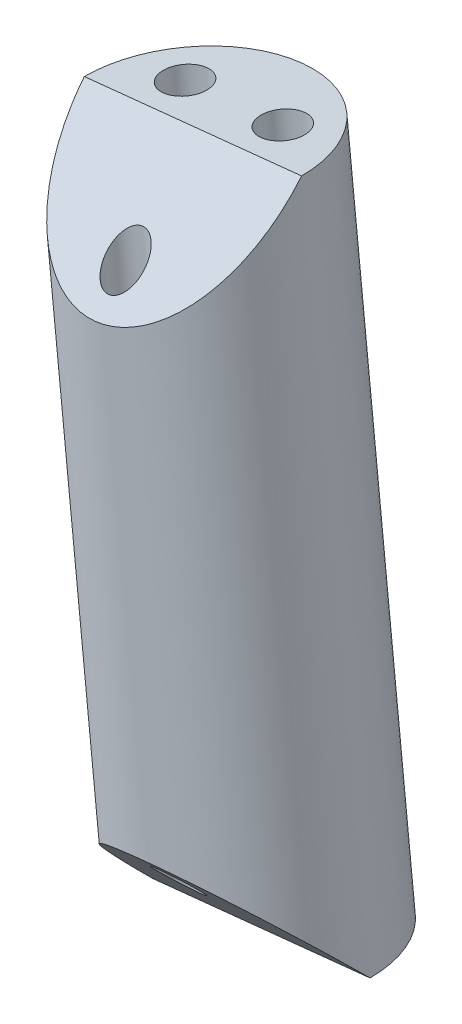
SolidWorks part; units mm, degrees
ref_plane "Front Plane" through (0, 0, 0) normal (0, 0, 1) x (1, 0, 0)
ref_plane "Top Plane" through (0, 0, 0) normal (0, 1, 0) x (1, 0, 0)
ref_plane "Right Plane" through (0, 0, 0) normal (1, 0, 0) x (0, 0, -1)
sketch "Sketch2" plane through (0, 0, 0) normal (0, 0, 1) x (1, 0, 0)
  line L0 (0, 0) -> (90, 0)
  line L1 (90, 0) -> (90, 120)
  line L2 (90, 120) -> (0, 120)
  line L3 (0, 120) -> (0, 0)
  line L4 (0, 120) -> (-10, 120)
  line L5 (-10, 120) -> (-10, 16.9491)
  line L6 (-10, 120) -> (57.5, 127)
  line L7 (57.5, 127) -> (90, 124)
  line L8 (90, 120) -> (99, 60)
  line L10 (90, 124) -> (90, 120)
  line L11 (5.9147, 0) -> (5.9147, -25)
  line L12 (5.9147, -25) -> (-4.0853, -25)
  line L13 (-4.0853, -29) -> (-4.0853, 0)
  line L14 (80, 0) -> (80, -25)
  line L15 (80, -25) -> (90, -25)
  line L16 (90, -29) -> (90, 0)
  line L17 (15.7927, 122.6748) -> (5.4776, 222.1414)
  line L18 (5.4776, 222.1414) -> (21.3923, 223.7918)
  line L19 (21.3923, 223.7918) -> (31.7073, 124.3252)
  line L20 (7.6492, 201.201) -> (23.5639, 202.8514)
  line L21 (10.9066, 169.7905) -> (26.8212, 171.441)
  line L22 (-10, 120) -> (-20.0396, 216.8108)
  line L23 (-20.0396, 216.8108) -> (-4.125, 218.4612)
  line L24 (-4.125, 218.4612) -> (5.9147, 121.6504)
  line L25 (-17.926, 196.4296) -> (-2.0114, 198.08)
  line L26 (-14.7556, 165.8578) -> (1.159, 167.5082)
  line L27 (57.5, 127) -> (46.9095, 229.1223)
  line L28 (46.9095, 229.1223) -> (30.9949, 227.4719)
  line L29 (30.9949, 227.4719) -> (41.5853, 125.3496)
  line L30 (33.2245, 205.9725) -> (49.1391, 207.6229)
  line L31 (36.5688, 173.7233) -> (52.4835, 175.3737)
  line L34 (90, 124) -> (99.1917, 223.5767)
  line L35 (99.1917, 223.5767) -> (83.2594, 225.0473)
  line L36 (83.2594, 225.0473) -> (74.0677, 125.4707)
  line L38 (81.3243, 204.0838) -> (97.2566, 202.6132)
  line L39 (78.4217, 172.6386) -> (94.354, 171.1679)
  line L40 (62.4078, 79.6749) -> (57.5, 127) construction
  line L41 (41.5853, 125.3496) -> (46.4931, 78.0244) construction
  line L42 (46.4931, 78.0244) -> (62.4078, 79.6749) construction
  line L43 (31.7073, 124.3252) -> (36.6151, 77.0001) construction
  line L44 (36.6151, 77.0001) -> (20.7005, 75.3496) construction
  line L45 (20.7005, 75.3496) -> (15.7927, 122.6748) construction
  line L46 (5.9147, 121.6504) -> (10.8224, 74.3253) construction
  line L47 (10.8224, 74.3253) -> (-5.0922, 72.6749) construction
  line L48 (-5.0922, 72.6749) -> (-10, 120) construction
  line L49 (74.0677, 125.4707) -> (69.6944, 78.0931) construction
  line L50 (69.6944, 78.0931) -> (85.7624, 78.0931) construction
  line L51 (85.7624, 78.0931) -> (90, 124) construction
  line L52 (-12.0823, 217.636) -> (10.4873, 0) construction
  line L53 (13.4349, 222.9666) -> (36.5574, 0) construction
  line L54 (38.9522, 228.2971) -> (62.6275, 0) construction
  line L55 (91.2256, 224.312) -> (70.5198, 0) construction
  line L59 (99, 60) -> (93.5277, 44.9649)
  line L60 (99, 60) -> (169.4769, 34.3485)
  line L61 (169.4769, 34.3485) -> (164.0046, 19.3134)
  line L62 (164.0046, 19.3134) -> (93.5277, 44.9649)
  line L63 (90, -2) -> (100, -2)
  line L64 (141.2862, 44.6091) -> (135.8138, 29.574)
  line L65 (99, 60) -> (55.7741, 75.7329) construction
  line L66 (55.7741, 75.7329) -> (50.3018, 60.6978) construction
  line L67 (100, -2) -> (100, -29)
  line L70 (-4.0853, -2) -> (-14.0853, -2)
  line L71 (-14.0853, -2) -> (-14.0853, -29)
  line L74 (-4.0853, 0) -> (0, 0)
  line L75 (-14.0853, -29) -> (-14.0853, -112.587)
  line L76 (-14.0853, -112.587) -> (100, -112.587)
  line L77 (100, -112.587) -> (100, -29)
  line L78 (-14.0853, -29) -> (100, -29)
  line L79 (-14.0853, -14.5) -> (100, -14.5) construction
  line L80 (31.7073, -112.587) -> (31.7073, -122.6232)
  line L81 (31.7073, -122.6232) -> (42.9573, -122.6232)
  line L82 (42.9573, -122.6232) -> (42.9573, -112.587)
  line L83 (-14.0853, -112.587) -> (-88.3667, -112.587)
  line L84 (-88.3667, -112.587) -> (-88.3667, -128.2699)
  line L85 (-88.3667, -128.2699) -> (169.4958, -128.2699)
  line L86 (169.4958, -128.2699) -> (169.4958, -112.587)
  line L87 (169.4958, -112.587) -> (100, -112.587)
  line L88 (90, 60) -> (-10, 60) construction
  line L89 (50.3018, 60.6978) -> (93.5277, 44.9649) construction
  line L90 (87.2806, 55.7521) -> (166.7408, 26.8309) construction
  line L91 (87.2806, 55.7521) -> (82.1749, 52.5336) construction
  line L92 (82.1749, 52.5336) -> (77.3257, 0) construction
  line L93 (83.1185, 56.6957) -> (86.337, 51.59) construction
  arc A0 (-10, 16.9491) -> (-4.0853, 0) centre (14.9876, 16.1624) ccw
  arc A1 (93.5277, 44.9649) -> (90, 0) centre (-126.4069, 39.5988) cw
  point P42 (41.1818, 206.7977)
  point P100 (84.7278, 54.1428)
  point P101 (84.7278, 54.1428)
  dimension "D11" = 47.3684
  dimension "D35" = 9
  dimension "D32" = 220
  dimension "D36" = 25
  dimension "D1" = 120
  dimension "D2" = 90
  dimension "D3" = 10
  dimension "D5" = 67.862
  dimension "D6" = 7
  dimension "D7" = 4
  dimension "D8" = 16
  dimension "D9" = 16
  dimension "D10" = 100
  dimension "D12" = 31.5789
  dimension "D13" = 16
  dimension "D14" = 16
  dimension "D15" = 16
  dimension "D16" = 25.7927
  dimension "D17" = 100
  dimension "D18" = 21.0526
  dimension "D19" = 31.5789
  dimension "D20" = 97.33
  dimension "D21" = 102.67
  dimension "D22" = 20.4905
  dimension "D23" = 30.7358
  dimension "D24" = 21.6147
  dimension "D25" = 32.4221
  dimension "D26" = 25
  dimension "D28" = 25
  dimension "D29" = 75
  dimension "D30" = 47.5789
  dimension "D31" = 30
  dimension "D33" = 46
  dimension "D34" = 20
  dimension "D37" = 2
  dimension "D38" = 2
  dimension "D39" = 27
  dimension "D40" = 10
  dimension "D41" = 10
  dimension "D42" = 27
  dimension "D43" = 14.5
  dimension "D44" = 127.5
ref_plane "Plane1" through (87.2806, 55.7521, 0) normal (-0.846, -0.5333, 0) x (0, 0, 1)
ref_plane "Plane2" through (82.1749, 52.5336, 0) normal (-0.0919, -0.9958, 0) x (-0.9958, 0.0919, 0)
ref_plane "Plane3" through (91.2256, 224.312, 0) normal (-0.0919, -0.9958, 0) x (-0.9958, 0.0919, 0)
ref_plane "Plane4" through (38.9522, 228.2971, 0) normal (0.1032, -0.9947, 0) x (-0.9947, -0.1032, 0)
ref_plane "Plane5" through (13.4349, 222.9666, 0) normal (0.1032, -0.9947, 0) x (-0.9947, -0.1032, 0)
ref_plane "Plane7" through (166.7408, 26.8309, 0) normal (0.9397, -0.342, 0) x (0, 0, -1)
ref_plane "Plane8" through (110.4217, -40.1902, 0) normal (0.9397, -0.342, 0) x (0, 0, -1)
ref_plane "Plane9" through (19.3664, 209.803, 0) normal (-0.0919, -0.9958, 0) x (-0.9958, 0.0919, 0)
ref_plane "Plane10" through (16.4638, 178.3578, 0) normal (-0.0919, -0.9958, 0) x (-0.9958, 0.0919, 0)
ref_plane "Plane11" through (-20.7793, 200.3721, 0) normal (0.1032, -0.9947, 0) x (-0.9947, -0.1032, 0)
ref_plane "Plane12" through (-17.435, 168.1229, 0) normal (0.1032, -0.9947, 0) x (-0.9947, -0.1032, 0)
ref_plane "Plane13" through (-20.5619, 198.2754, 0) normal (0.1032, -0.9947, 0) x (-0.9947, -0.1032, 0)
ref_plane "Plane14" through (-17.3045, 166.8649, 0) normal (0.1032, -0.9947, 0) x (-0.9947, -0.1032, 0)
ref_plane "Plane15" through (-12.0823, 217.636, 0) normal (0.1032, -0.9947, 0) x (-0.9947, -0.1032, 0)
ref_plane "Plane16" through (-20.3445, 196.1788, 0) normal (0.1032, -0.9947, 0) x (-0.9947, -0.1032, 0)
ref_plane "Plane17" through (-17.1741, 165.607, 0) normal (0.1032, -0.9947, 0) x (-0.9947, -0.1032, 0)
ref_plane "Plane18" through (12.1098, 131.1899, 0) normal (-0.0919, -0.9958, 0) x (-0.9958, 0.0919, 0)
ref_plane "Plane19" through (-12.4184, 119.7492, 0) normal (0.1032, -0.9947, 0) x (-0.9947, -0.1032, 0)
ref_plane "Plane20" through (0, 0, 0) normal (0, 0, 1) x (0.1032, -0.9947, 0)
ref_plane "Plane21" through (0, 0, 0) normal (0, 0, 1) x (-0.0919, -0.9958, 0)
ref_plane "Plane22" through (10.3758, 1.076, 0) normal (-0.9947, -0.1032, 0) x (0.1032, -0.9947, 0)
ref_plane "Plane23" through (36.1684, 3.7508, 0) normal (-0.9947, -0.1032, 0) x (0.1032, -0.9947, 0)
ref_plane "Plane24" through (61.9611, 6.4256, 0) normal (-0.9947, -0.1032, 0) x (0.1032, -0.9947, 0)
ref_plane "Plane25" through (69.924, -6.4545, 0) normal (-0.9958, 0.0919, 0) x (-0.0919, -0.9958, 0)
sketch "Sketch3" plane through (-20.3445, 196.1788, 0) normal (0.1032, -0.9947, 0) x (-0.9947, -0.1032, 0)
  line L0 (-2.4314, 0) -> (-18.4314, 0) construction
  circle A0 centre (-10.4314, 0) radius 8
  dimension "D1" = 16
extrude "Boss-Extrude1" add sketch "Sketch3" along normal blind 48.6332
sketch "Sketch4" plane through (10.3758, 1.076, 0) normal (-0.9947, -0.1032, 0) x (0.1032, -0.9947, 0)
  line L0 (-197.2309, 0) -> (-189.2309, 8)
  line L1 (-197.2309, 8) -> (-197.2309, -8) construction
  line L2 (-148.5977, 8) -> (-197.2309, 8) construction
  line L3 (-189.2309, 8) -> (-197.2309, 8)
  line L4 (-197.2309, 8) -> (-197.2309, 0)
  line L5 (-156.5977, 8) -> (-148.5977, 8)
  line L6 (-148.5977, 8) -> (-148.5977, 0)
  line L7 (-217.7214, 0) -> (1.0818, 0) construction
  line L8 (-148.5977, 0) -> (-156.5977, 8)
  dimension "D1" = 45
  dimension "D2" = 45
extrude "Cut-Extrude1" cut sketch "Sketch4" against normal through all and the other way through all
sketch "Sketch5" plane through (10.3758, 1.076, 0) normal (-0.9947, -0.1032, 0) x (0.1032, -0.9947, 0)
  line L0 (-148.5977, 0) -> (-152.5977, 4)
  line L1 (-148.5977, 0) -> (-156.5977, 8) construction
  line L2 (-152.5977, 4) -> (-144.5977, 4)
  line L3 (-144.5977, 4) -> (-144.5977, 0)
  line L4 (-213.7055, 0) -> (7.2742, 0) construction
  line L6 (-148.5977, 0) -> (-144.5977, 4) construction
  line L7 (-144.5977, 0) -> (-148.5977, -4)
  line L8 (-148.5977, -8) -> (-148.5977, 0) construction
  line L9 (-148.5977, 0) -> (-148.5977, -4)
  dimension "D1" = 4
  dimension "D2" = 45
sketch "Sketch7" plane through (10.3758, 1.076, 0) normal (-0.9947, -0.1032, 0) x (0.1032, -0.9947, 0)
  line L0 (-193.2309, 4) -> (-197.2309, 0)
  line L1 (-217.7214, 0) -> (1.0818, 0) construction
  line L4 (-197.2309, -4) -> (-197.2309, 0)
  line L5 (-193.2309, 4) -> (-193.2309, 0)
  arc A0 (-197.2309, -4) -> (-193.2309, 0) centre (-197.2309, 0) ccw
  dimension "D1" = 4
  dimension "D2" = 4
sketch "Sketch8" plane through (-20.3445, 196.1788, 0) normal (-0.1032, 0.9947, 0) x (0.9947, 0.1032, 0)
  line L0 (2.4314, 0) -> (18.4314, 0) construction
  circle A0 centre (10.4314, -5.5) radius 1.4
  circle A1 centre (6.8314, 3) radius 1.6
  circle A2 centre (14.0314, 3) radius 1.6
  point P9 (10.4314, 0)
  dimension "D1" = 3.2
  dimension "D2" = 3.2
  dimension "D3" = 2.8
  dimension "D4" = 3
  dimension "D5" = 5.5
  dimension "D6" = 3.6
  dimension "D7" = 3.6
  dimension "D8" = 3
extrude "Cut-Extrude3" cut sketch "Sketch8" against normal through all and the other way through all
sketch "Sketch9" plane through (-20.3445, 196.1788, 0) normal (-0.1032, 0.9947, 0) x (0.9947, 0.1032, 0)
  line L0 (4.5289, 5.4) -> (16.3339, 5.4)
  line L1 (-101.1265, 0) -> (155.3606, 0) construction
  arc A0 (18.4314, 0) -> (2.4314, 0) centre (10.4314, 0) ccw construction
  arc A1 (4.5289, 5.4) -> (16.3339, 5.4) centre (10.4314, 0) cw
  dimension "D1" = 5.4
